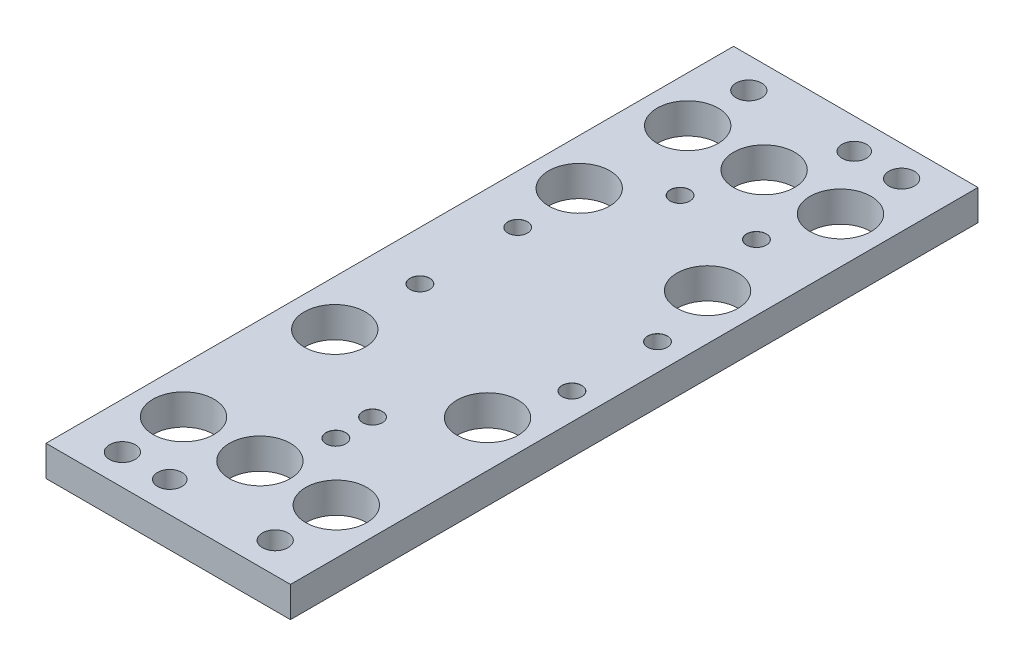
SolidWorks part; units mm, degrees
material "K110"
ref_plane "Front Plane" through (0, 0, 0) normal (0, 0, 1) x (1, 0, 0)
ref_plane "Top Plane" through (0, 0, 0) normal (0, 1, 0) x (1, 0, 0)
ref_plane "Right Plane" through (0, 0, 0) normal (1, 0, 0) x (0, 0, -1)
sketch "Sketch1" plane through (0, 0, 0) normal (0, 1, 0) x (1, 0, 0)
  line L1 (-40, -112.5) -> (40, -112.5)
  line L2 (-40, -112.5) -> (-40, 112.5)
  line L3 (-40, 112.5) -> (40, 112.5)
  line L4 (40, -112.5) -> (40, 112.5)
  line L5 (-40, -112.5) -> (40, 112.5) construction
  line L6 (-40, 112.5) -> (40, -112.5) construction
  point P0 (0, 0)
  dimension "D1" = 225
  dimension "D2" = 80
extrude "Boss-Extrude1" add sketch "Sketch1" against normal blind 10
sketch "Sketch2" plane through (0, 0, 0) normal (0, 1, 0) x (1, 0, 0)
  circle A0 centre (25, -82.5) radius 10 construction
  circle A1 centre (0, -82.5) radius 10 construction
  circle A2 centre (-25, -82.5) radius 10 construction
  circle A3 centre (25, -33) radius 10 construction
  circle A4 centre (-25, -33) radius 10 construction
  circle A6 centre (25, 39) radius 10 construction
  circle A7 centre (-25, 47) radius 10 construction
  circle A8 centre (-25, 82.5) radius 10 construction
  circle A9 centre (0, 82.5) radius 10 construction
  circle A10 centre (25, 82.5) radius 10 construction
  circle A11 centre (25, -82.5) radius 10
  circle A12 centre (0, -82.5) radius 10
  circle A13 centre (-25, -82.5) radius 10
  circle A14 centre (25, -33) radius 10
  circle A15 centre (-25, -33) radius 10
  circle A17 centre (25, 39) radius 10
  circle A18 centre (-25, 47) radius 10
  circle A19 centre (-25, 82.5) radius 10
  circle A20 centre (0, 82.5) radius 10
  circle A21 centre (25, 82.5) radius 10
extrude "Cut-Extrude1" cut sketch "Sketch2" against normal up to next
hole_wizard "M8 Clearance Hole1" positions "Sketch9" profile "Sketch8" hole size "M8" standard "ISO" end condition through all
sketch "Sketch9" plane through (0, 0, 0) normal (0, 1, 0) x (1, 0, 0)
  point P0 (25, -102.5)
  point P3 (-25, -102.5)
  point P6 (25, 102.5)
  point P9 (-25, 102.5)
sketch "Sketch8" plane through (25, 0, 102.5) normal (1, 0, 0) x (0, 0, 1)
  line L0 (0, 0) -> (0, 10)
  line L1 (0, 10) -> (4.2, 10)
  line L2 (4.2, 10) -> (4.2, 0)
  line L5 (4.2, 0) -> (0, 0)
  line L11 (0, -6.35) -> (0, 107.95) construction
  dimension "Thru Hole Dia." = 8.4
  dimension "Thru Hole Depth" = 10
hole_wizard "Ø8.0mm Dowel Hole1" positions "Sketch12" profile "Sketch11" hole size "Ø8.0" standard "ISO" end condition through all
sketch "Sketch12" plane through (0, 0, 0) normal (0, 1, 0) x (1, 0, 0)
  point P0 (-9.5, -102.5)
  point P3 (9.5, 102.5)
sketch "Sketch11" plane through (-9.5, 0, 102.5) normal (1, 0, 0) x (0, 0, 1)
  line L0 (0, 0) -> (0, 10)
  line L1 (0, 10) -> (4, 10)
  line L2 (4, 10) -> (4, 0)
  line L5 (4, 0) -> (0, 0)
  line L11 (0, -6.35) -> (0, 107.95) construction
  dimension "Thru Hole Dia." = 8
  dimension "Thru Hole Depth" = 10
hole_wizard "M6 Clearance Hole1" positions "Sketch15" profile "Sketch14" hole size "M6" standard "ISO" end condition through all
sketch "Sketch15" plane through (0, 0, 0) normal (0, 1, 0) x (1, 0, 0)
  point P0 (-24, -6.14)
  point P3 (-24, 25.86)
  point P6 (31.25, -11.64)
  point P9 (31.25, 16.36)
  point P12 (18.5, 61.5)
  point P15 (-6.5, 61.5)
  point P18 (6, -51.64)
  point P21 (6, -63.64)
sketch "Sketch14" plane through (-24, 0, 6.14) normal (1, 0, 0) x (0, 0, 1)
  line L0 (0, 0) -> (0, 10)
  line L1 (0, 10) -> (3.2, 10)
  line L2 (3.2, 10) -> (3.2, 0.025)
  line L3 (3.2, 0.025) -> (3.225, 0)
  line L5 (3.225, 0) -> (0, 0)
  line L6 (-3.2, 0.025) -> (-3.225, 0) construction
  line L11 (0, -6.35) -> (0, 107.95) construction
  dimension "Thru Hole Dia." = 6.4
  dimension "Thru Hole Depth" = 10
  dimension "Near C'Sink Dia." = 6.45
  dimension "Near C'Sink Angle" = 90
